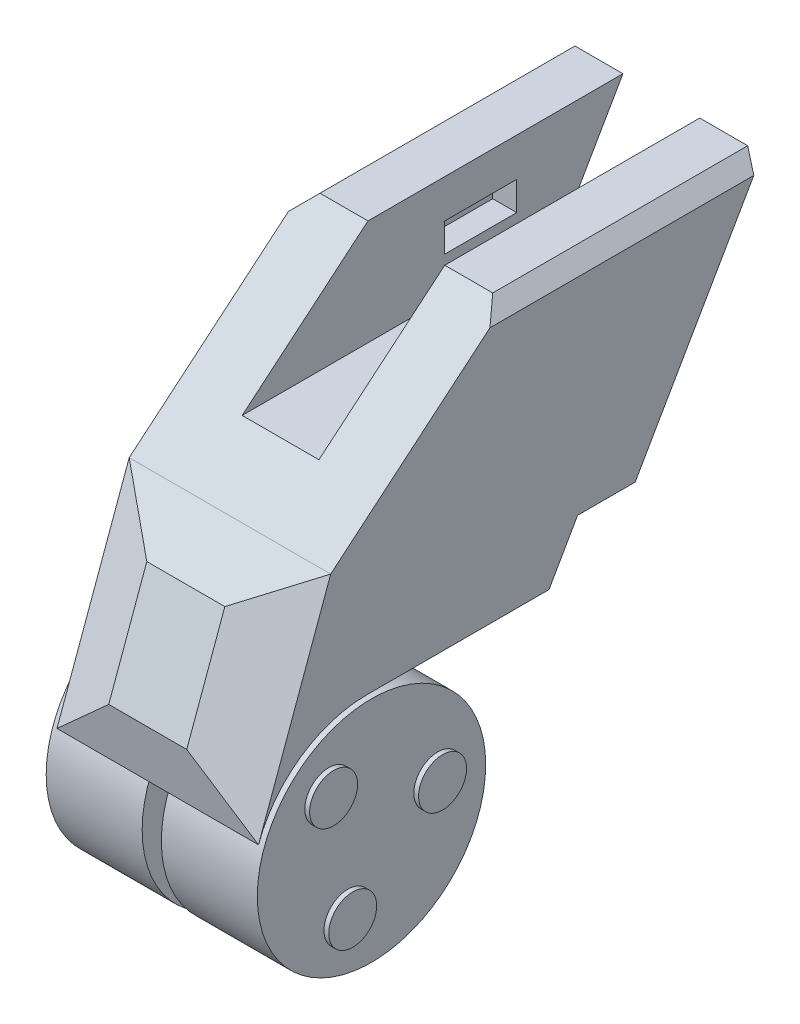
SolidWorks part; units mm, degrees
ref_plane "Front Plane" through (0, 0, 0) normal (0, 0, 1) x (1, 0, 0)
ref_plane "Top Plane" through (0, 0, 0) normal (0, 1, 0) x (1, 0, 0)
ref_plane "Right Plane" through (0, 0, 0) normal (1, 0, 0) x (0, 0, -1)
sketch "Sketch1" plane through (0, 0, 0) normal (1, 0, 0) x (0, 0, -1)
  circle A0 centre (0, 0) radius 11.9
  dimension "D1" = 23.8
extrude "Boss-Extrude1" add sketch "Sketch1" along normal blind 10 from offset 1
extrude "Boss-Extrude2" add sketch "Sketch1<2>" against normal blind 10 from offset 1 separate body offset against normal yes
sketch "Sketch1<2>" plane through (0, 0, 0) normal (1, 0, 0) x (0, 0, -1) same geometry as "Sketch1"
sketch "Sketch2" plane through (-1, 0, 0) normal (1, 0, 0) x (0, 0, -1)
  circle A0 centre (0, 0) radius 6
  dimension "D1" = 12
extrude "Cut-Extrude1" cut sketch "Sketch2" against normal blind 4
mirror "Mirror1" about plane through (0, 0, 0) normal (1, 0, 0) of "Cut-Extrude1"
sketch "Sketch3" plane through (0, 0, 0) normal (1, 0, 0) x (0, 0, -1)
  line L0 (0, 12) -> (19, 12)
  line L1 (19, 12) -> (21.9747, 17.2107)
  line L2 (21.9747, 17.2107) -> (27.9747, 17.2107)
  line L3 (27.9747, 17.2107) -> (41.2033, 40.2044)
  line L4 (-11.2763, 4.1042) -> (-3.7519, 24.7775)
  line L6 (-3.7519, 24.7775) -> (14.6332, 40.2044)
  line L7 (14.6332, 40.2044) -> (41.2033, 40.2044)
  line L8 (-3.7519, 24.7775) -> (-3.1903, 26.3204) construction
  arc A0 (-11.2763, 4.1042) -> (0, 12) centre (0, 0) cw
  dimension "D8" = 12
  dimension "D1" = 6
  dimension "D2" = 6
  dimension "D3" = 19
  dimension "D4" = 70
  dimension "D5" = 22
  dimension "D6" = 24
  dimension "D7" = 30
extrude "Boss-Extrude3" add sketch "Sketch3" along normal mid plane 21 separate body
sketch "Sketch4" plane through (0, 4.1042, 11.2763) normal (0, 0.342, 0.9397) x (1, 0, 0)
  line L1 (-10.5, 22) -> (10.5, 22)
  line L2 (-10.5, 22) -> (-10.5, 0)
  line L3 (-10.5, 0) -> (10.5, 0)
  line L4 (10.5, 22) -> (10.5, 0)
extrude "Boss-Extrude4" add sketch "Sketch4" along normal blind 3
chamfer "Chamfer1" distance 3 angle 60 2 edges at (0, 25.8035, 6.5709) (0, 5.1303, 14.0954) first distance on face at (0, 25.2905, 5.1614) first distance on face at (0, 4.6173, 12.6859)
chamfer "Chamfer2" distance 3 angle 65 2 edges at (10.5, 15.4669, 10.3332) (-10.5, 15.4669, 10.3332) first distance on face at (10.5, 20.0423, -8.7847) first distance on face at (-10.5, 20.0423, -8.7847)
sketch "Sketch5" plane through (11, 0, 0) normal (1, 0, 0) x (0, 0, -1)
  circle A0 centre (-4.4491, 5.4042) radius 2.5
  circle A1 centre (6.9047, 1.151) radius 2.5
  circle A2 centre (-2.4556, -6.5552) radius 2.5
  dimension "D1" = 5
  dimension "D2" = 7
  dimension "D3" = 3
extrude "Boss-Extrude5" add sketch "Sketch5" along normal blind 0.5
mirror "Mirror2" about plane through (0, 0, 0) normal (1, 0, 0) of "Boss-Extrude5"
sketch "Sketch7" plane through (0, 0, 0) normal (0, 0, 1) x (1, 0, 0)
  line L1 (4, 29.2044) -> (-4, 29.2044)
  line L2 (4, 29.2044) -> (4, 40.2044)
  line L3 (4, 40.2044) -> (-4, 40.2044)
  line L4 (-4, 29.2044) -> (-4, 40.2044)
  line L7 (10.5, 40.2044) -> (-10.5, 40.2044) construction
  point P4 (0, 29.2044)
  dimension "D1" = 8
  dimension "D2" = 11
extrude "Cut-Extrude2" cut sketch "Sketch7" against normal through all
chamfer "Chamfer3" distance 1.5 angle 45 2 edges at (10.5, 40.2044, -27.9183) (-10.5, 40.2044, -27.9183)
scale "Scale2" bodies to scale 108 109 107 scale about origin uniform scaling yes scale factor 2
sketch "Sketch9" plane through (-8, 0, 0) normal (1, 0, 0) x (0, 0, -1)
  line L0 (69.7497, 58.4088) -> (3.0478, 58.4088) construction
  line L1 (45.2664, 72.4088) -> (60.2664, 72.4088)
  line L2 (45.2664, 72.4088) -> (45.2664, 66.4088)
  line L3 (45.2664, 66.4088) -> (60.2664, 66.4088)
  line L4 (60.2664, 72.4088) -> (60.2664, 66.4088)
  dimension "D1" = 8
  dimension "D2" = 6
  dimension "D3" = 15
  dimension "D4" = 16
extrude "Cut-Extrude3" cut sketch "Sketch9" against normal blind 5
mirror "Mirror3" about plane through (0, 0, 0) normal (1, 0, 0) of "Cut-Extrude3"
